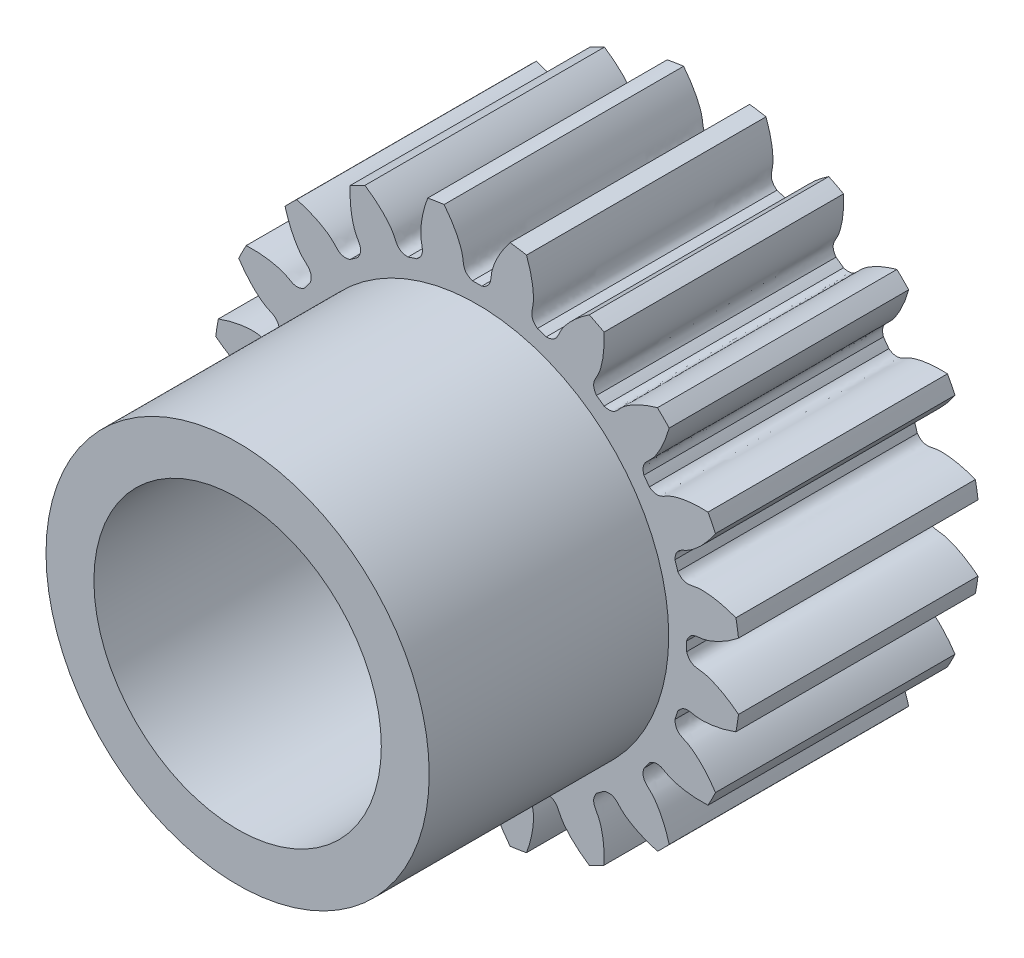
SolidWorks part; units mm, degrees
ref_plane "前视基准面" through (0, 0, 0) normal (0, 0, 1) x (1, 0, 0)
ref_plane "上视基准面" through (0, 0, 0) normal (0, 1, 0) x (1, 0, 0)
ref_plane "右视基准面" through (0, 0, 0) normal (1, 0, 0) x (0, 0, -1)
sketch "草图1" plane through (0, 0, 0) normal (0, 0, 1) x (1, 0, 0)
  circle A0 centre (0, 0) radius 11
extrude "凸台-拉伸1" add sketch "草图1" along normal blind 10
ref_axis "基准轴1" through (0, 0, -0.5) along (0, 0, 1)
sketch "草图2" plane through (0, 0, 0) normal (0, 0, 1) x (1, 0, 0)
  line L0 (0, 0) -> (0, 11) construction
  circle A0 centre (0, 0) radius 11 construction
  arc A1 (0.1933, 8.7479) -> (-0.1933, 8.7479) centre (0, 0) ccw
  arc A2 (3.1812, 12.4983) -> (-3.1812, 12.4983) centre (0, 0) ccw
  spline S0 degree 3 poles (0.1933, 8.7479) (0.6112, 8.8935) (0.5571, 9.1871) (0.6129, 9.47) (0.6189, 9.4976) (0.6263, 9.5286) (0.6353, 9.5632) (0.646, 9.6012) (0.6585, 9.6426) (0.673, 9.6873) (0.6897, 9.7352) (0.7086, 9.7863) (0.7299, 9.8406) (0.7537, 9.8978) (0.7801, 9.958) (0.8094, 10.0211) (0.8415, 10.087) (0.8767, 10.1556) (0.915, 10.2267) (0.9566, 10.3004) (1.0015, 10.3764) (1.05, 10.4548) (1.102, 10.5352) (1.1578, 10.6178) (1.2173, 10.7023) (1.2808, 10.7886) (1.3482, 10.8766) (1.4198, 10.9662) (1.4955, 11.0572) (1.5755, 11.1496) (1.6598, 11.2431) (1.7486, 11.3376) (1.8418, 11.4331) (1.9397, 11.5293) (2.0421, 11.6261) (2.1493, 11.7233) (2.2612, 11.8209) (2.378, 11.9186) (2.4996, 12.0163) (2.6261, 12.1139) (2.7575, 12.2112) (2.9415, 12.3416) (3.0839, 12.4363) (3.1812, 12.4983) knots 0 0 0 0 0.165916 0.170906 0.176664 0.183189 0.190482 0.198542 0.207371 0.216967 0.22733 0.238462 0.250361 0.263027 0.276462 0.290664 0.305634 0.321371 0.337876 0.355149 0.37319 0.391998 0.411574 0.431917 0.453028 0.474907 0.497554 0.520968 0.54515 0.570099 0.595817 0.622302 0.649554 0.677575 0.706363 0.735918 0.766242 0.797333 0.829191 0.861818 0.895212 0.929373 1 1 1 1
  spline S1 degree 3 poles (-0.1933, 8.7479) (-0.6112, 8.8935) (-0.5571, 9.1871) (-0.6129, 9.47) (-0.6189, 9.4976) (-0.6263, 9.5286) (-0.6353, 9.5632) (-0.646, 9.6012) (-0.6585, 9.6426) (-0.673, 9.6873) (-0.6897, 9.7352) (-0.7086, 9.7863) (-0.7299, 9.8406) (-0.7537, 9.8978) (-0.7801, 9.958) (-0.8094, 10.0211) (-0.8415, 10.087) (-0.8767, 10.1556) (-0.915, 10.2267) (-0.9566, 10.3004) (-1.0015, 10.3764) (-1.05, 10.4548) (-1.102, 10.5352) (-1.1578, 10.6178) (-1.2173, 10.7023) (-1.2808, 10.7886) (-1.3482, 10.8766) (-1.4198, 10.9662) (-1.4955, 11.0572) (-1.5755, 11.1496) (-1.6598, 11.2431) (-1.7486, 11.3376) (-1.8418, 11.4331) (-1.9397, 11.5293) (-2.0421, 11.6261) (-2.1493, 11.7233) (-2.2612, 11.8209) (-2.378, 11.9186) (-2.4996, 12.0163) (-2.6261, 12.1139) (-2.7575, 12.2112) (-2.9415, 12.3416) (-3.0839, 12.4363) (-3.1812, 12.4983) knots 0 0 0 0 0.165916 0.170906 0.176664 0.183189 0.190482 0.198542 0.207371 0.216967 0.22733 0.238462 0.250361 0.263027 0.276462 0.290664 0.305634 0.321371 0.337876 0.355149 0.37319 0.391998 0.411574 0.431917 0.453028 0.474907 0.497554 0.520968 0.54515 0.570099 0.595817 0.622302 0.649554 0.677575 0.706363 0.735918 0.766242 0.797333 0.829191 0.861818 0.895212 0.929373 1 1 1 1
extrude "切除-拉伸1" cut sketch "草图2" along normal through all
pattern_circular "阵列(圆周)1" count 20 every 18 about axis through (0, 0, -0.5) along (0, 0, 1) of "切除-拉伸1"
sketch "草图3" plane through (0, 0, 0) normal (0, 0, 1) x (1, 0, 0)
  circle A0 centre (0, 0) radius 10 construction
  dimension "Dn" = 20
sketch "草图4" plane through (0, 0, 10) normal (0, 0, 1) x (1, 0, 0)
  circle A0 centre (0, 0) radius 8
  dimension "D1" = 16
extrude "凸台-拉伸2" add sketch "草图4" along normal blind 10
sketch "草图5" plane through (0, 0, 20) normal (0, 0, 1) x (1, 0, 0)
  circle A0 centre (0, 0) radius 6
  dimension "D1" = 12
extrude "切除-拉伸2" cut sketch "草图5" against normal through all
